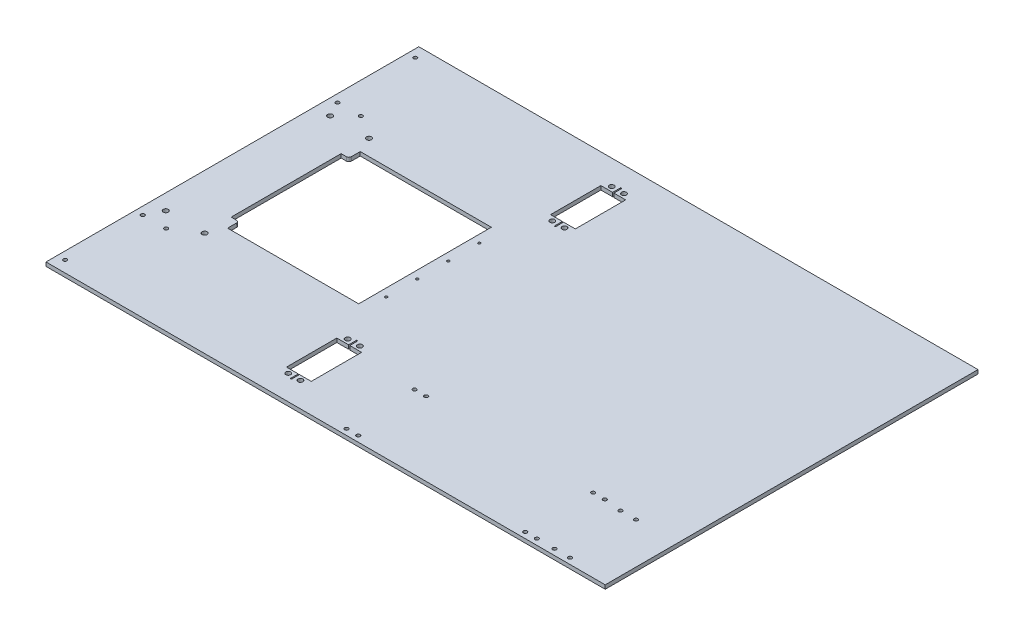
SolidWorks part; units mm, degrees
ref_plane "Front Plane" through (0, 0, 0) normal (0, 0, 1) x (1, 0, 0)
ref_plane "Top Plane" through (0, 0, 0) normal (0, 1, 0) x (1, 0, 0)
ref_plane "Right Plane" through (0, 0, 0) normal (1, 0, 0) x (0, 0, -1)
sketch "Sketch1" plane through (0, 0, 0) normal (0, 1, 0) x (1, 0, 0)
  line L1 (-228.6, -152.4) -> (228.6, -152.4)
  line L2 (-228.6, -152.4) -> (-228.6, 152.4)
  line L3 (-228.6, 152.4) -> (228.6, 152.4)
  line L4 (228.6, -152.4) -> (228.6, 152.4)
  line L5 (-228.6, -152.4) -> (228.6, 152.4) construction
  line L6 (-228.6, 152.4) -> (228.6, -152.4) construction
  point P0 (0, 0)
  dimension "D1" = 304.8
  dimension "D2" = 457.2
extrude "Boss-Extrude1" add sketch "Sketch1" along normal blind 3.175 contours L3 L4 L1 L2
sketch "Sketch2" plane through (0, 3.175, 0) normal (0, 1, 0) x (1, 0, 0)
  circle A0 centre (-184.15, -67.1976) radius 2.0635 construction
  circle A1 centre (-215.9, -67.1976) radius 2.0635 construction
  circle A2 centre (-184.15, 67.1976) radius 2.0635 construction
  circle A3 centre (-215.9, 67.1976) radius 2.0635 construction
  circle A6 centre (-184.15, -67.1976) radius 2.0635
  circle A7 centre (-215.9, -67.1976) radius 2.0635
  circle A8 centre (-184.15, 67.1976) radius 2.0635
  circle A9 centre (-215.9, 67.1976) radius 2.0635
extrude "Cut-Extrude1" cut sketch "Sketch2" against normal through all
sketch "Sketch3" plane through (0, 3.175, 0) normal (0, 1, 0) x (1, 0, 0)
  line L0 (-228.6, 0) -> (228.6, 0) construction
  line L1 (-228.6, -152.4) -> (-228.6, 152.4) construction
  line L2 (228.6, -152.4) -> (228.6, 152.4) construction
sketch "Sketch4" plane through (0, 3.175, 0) normal (0, 1, 0) x (1, 0, 0)
  line L0 (-184.658, 44.958) -> (-184.658, -44.958)
  line L1 (-184.658, -44.958) -> (-180.34, -44.958)
  line L2 (-178.308, -46.99) -> (-178.308, -54.229)
  line L3 (-178.308, -54.229) -> (-71.12, -54.229)
  line L4 (-71.12, -54.229) -> (-71.12, 54.229)
  line L5 (-71.12, 54.229) -> (-178.308, 54.229)
  line L6 (-178.308, 54.229) -> (-178.308, 46.99)
  line L7 (-180.34, 44.958) -> (-184.658, 44.958)
  line L8 (-184.15, 44.45) -> (-184.15, -44.45)
  line L9 (-180.34, 44.45) -> (-184.15, 44.45)
  line L10 (-177.8, 53.721) -> (-177.8, 46.99)
  line L11 (-71.628, 53.721) -> (-177.8, 53.721)
  line L12 (-71.628, -53.721) -> (-71.628, 53.721)
  line L13 (-177.8, -53.721) -> (-71.628, -53.721)
  line L14 (-177.8, -46.99) -> (-177.8, -53.721)
  line L15 (-184.15, -44.45) -> (-180.34, -44.45)
  line L16 (-184.15, 44.45) -> (-184.15, -44.45) construction
  line L17 (-180.34, 44.45) -> (-184.15, 44.45) construction
  line L18 (-177.8, 53.721) -> (-177.8, 46.99) construction
  line L19 (-71.628, 53.721) -> (-177.8, 53.721) construction
  line L20 (-71.628, -53.721) -> (-71.628, 53.721) construction
  line L21 (-177.8, -53.721) -> (-71.628, -53.721) construction
  line L22 (-177.8, -46.99) -> (-177.8, -53.721) construction
  line L23 (-184.15, -44.45) -> (-180.34, -44.45) construction
  arc A0 (-178.308, -46.99) -> (-180.34, -44.958) centre (-180.34, -46.99) ccw
  arc A1 (-180.34, 44.958) -> (-178.308, 46.99) centre (-180.34, 46.99) ccw
  arc A2 (-180.34, 44.45) -> (-177.8, 46.99) centre (-180.34, 46.99) ccw
  arc A3 (-177.8, -46.99) -> (-180.34, -44.45) centre (-180.34, -46.99) ccw
  arc A4 (-180.34, 44.45) -> (-177.8, 46.99) centre (-180.34, 46.99) ccw construction
  arc A5 (-177.8, -46.99) -> (-180.34, -44.45) centre (-180.34, -46.99) ccw construction
  dimension "D1" = 0
  dimension "D2" = 0.508
extrude "Cut-Extrude2" cut sketch "Sketch4" against normal up to next
sketch "Sketch5" plane through (0, 3.175, 0) normal (0, 1, 0) x (1, 0, 0)
  circle A0 centre (-203.2, 79.629) radius 1.5 construction
  circle A1 centre (-222.25, 143.129) radius 1.5 construction
  circle A2 centre (-222.25, 79.629) radius 1.5 construction
  circle A3 centre (-203.2, -79.629) radius 1.5 construction
  circle A4 centre (-222.25, -79.629) radius 1.5 construction
  circle A5 centre (-222.25, -143.129) radius 1.5 construction
  circle A6 centre (-203.2, 79.629) radius 1.5
  circle A7 centre (-222.25, 143.129) radius 1.5
  circle A8 centre (-222.25, 79.629) radius 1.5
  circle A9 centre (-203.2, -79.629) radius 1.5
  circle A10 centre (-222.25, -79.629) radius 1.5
  circle A11 centre (-222.25, -143.129) radius 1.5
extrude "Cut-Extrude3" cut sketch "Sketch5" against normal through all
sketch "Sketch7" plane through (0, 3.175, 0) normal (0, 1, 0) x (1, 0, 0)
  line L0 (-55.847, -87.373) -> (-35.593, -128.527) construction
  line L1 (-55.847, -87.373) -> (-46.22, -87.373)
  line L2 (-55.847, -87.373) -> (-55.847, -128.527)
  line L3 (-55.847, -128.527) -> (-46.22, -128.527)
  line L4 (-35.593, -87.373) -> (-35.593, -128.527)
  line L5 (-35.593, -87.373) -> (-55.847, -128.527) construction
  line L6 (-50.72, -83.65) -> (-40.72, -132.25) construction
  line L7 (-50.72, -132.25) -> (-40.72, -83.65) construction
  line L9 (-228.6, -152.4) -> (228.6, -152.4) construction
  line L10 (-45.22, -128.527) -> (-35.593, -128.527)
  line L12 (-46.22, -128.527) -> (-46.22, -135.131)
  line L13 (-46.22, -135.131) -> (-45.22, -135.131)
  line L14 (-45.22, -128.527) -> (-45.22, -135.131)
  line L15 (-45.72, -107.95) -> (-2.6371, -107.95) construction
  line L16 (-46.22, -80.769) -> (-45.22, -80.769)
  line L17 (-46.22, -87.373) -> (-46.22, -80.769)
  line L18 (-45.22, -87.373) -> (-45.22, -80.769)
  line L19 (-45.22, -87.373) -> (-35.593, -87.373)
  line L20 (-228.6, -152.4) -> (-228.6, 152.4) construction
  circle A0 centre (-50.72, -132.25) radius 2
  circle A1 centre (-40.72, -132.25) radius 2
  circle A2 centre (-50.72, -83.65) radius 2
  circle A3 centre (-40.72, -83.65) radius 2
  point P8 (-45.72, -135.131)
  point P17 (-45.72, -107.95)
  point P18 (-45.72, -107.95)
  dimension "D1" = 41.154
  dimension "D3" = 20.254
  dimension "D5" = 4
  dimension "D6" = 44.45
  dimension "D2" = 10
  dimension "D4" = 48.6
  dimension "D7" = 1
  dimension "D8" = 6.604
  dimension "D9" = 182.88
extrude "Cut-Extrude5" cut sketch "Sketch7" against normal through all
mirror "Mirror1" about plane through (0, 0, 0) normal (0, 0, 1) of "Cut-Extrude5"
sketch "Sketch8" plane through (0, 3.175, 0) normal (0, 1, 0) x (1, 0, 0)
  circle A1 centre (-64.77, -38.1) radius 1
  circle A2 centre (-64.77, -38.1) radius 1
  circle A3 centre (-64.77, -12.7) radius 1
  circle A4 centre (-64.77, -12.7) radius 1
  circle A5 centre (-64.77, 12.7) radius 1
  circle A6 centre (-64.77, 12.7) radius 1
  circle A7 centre (-64.77, 38.1) radius 1
  circle A8 centre (-64.77, 38.1) radius 1
  dimension "D1" = 0
  dimension "D2" = 0
  dimension "D3" = 0
  dimension "D4" = 0
extrude "Cut-Extrude6" cut sketch "Sketch8" against normal through all
sketch "Sketch12" plane through (0, 3.175, 0) normal (0, 1, 0) x (1, 0, 0)
  circle A0 centre (195.024, -93.6625) radius 1.5 construction
  circle A1 centre (182.324, -93.6625) radius 1.5 construction
  circle A2 centre (195.024, -147.6375) radius 1.5 construction
  circle A3 centre (182.324, -147.6375) radius 1.5 construction
  circle A4 centre (167.9575, -92.075) radius 1.5 construction
  circle A5 centre (158.4325, -92.075) radius 1.5 construction
  circle A6 centre (167.9575, -147.6375) radius 1.5 construction
  circle A7 centre (158.4325, -147.6375) radius 1.5 construction
  circle A8 centre (21.9075, -147.6375) radius 1.5 construction
  circle A9 centre (12.3825, -147.6375) radius 1.5 construction
  circle A10 centre (12.3825, -92.075) radius 1.5 construction
  circle A11 centre (21.9075, -92.075) radius 1.5 construction
  circle A12 centre (195.024, -93.6625) radius 1.5
  circle A13 centre (182.324, -93.6625) radius 1.5
  circle A14 centre (195.024, -147.6375) radius 1.5
  circle A15 centre (182.324, -147.6375) radius 1.5
  circle A16 centre (167.9575, -92.075) radius 1.5
  circle A17 centre (158.4325, -92.075) radius 1.5
  circle A18 centre (167.9575, -147.6375) radius 1.5
  circle A19 centre (158.4325, -147.6375) radius 1.5
  circle A20 centre (21.9075, -147.6375) radius 1.5
  circle A21 centre (12.3825, -147.6375) radius 1.5
  circle A22 centre (12.3825, -92.075) radius 1.5
  circle A23 centre (21.9075, -92.075) radius 1.5
extrude "Cut-Extrude7" cut sketch "Sketch12" against normal through all
equation "\"tightTol\"= 0.005in"
equation "\"normTol\"= 0.01in"
equation "\"looseTol\"= 0.02in"
equation "\"D2@Sketch4\"=\"looseTol\""
